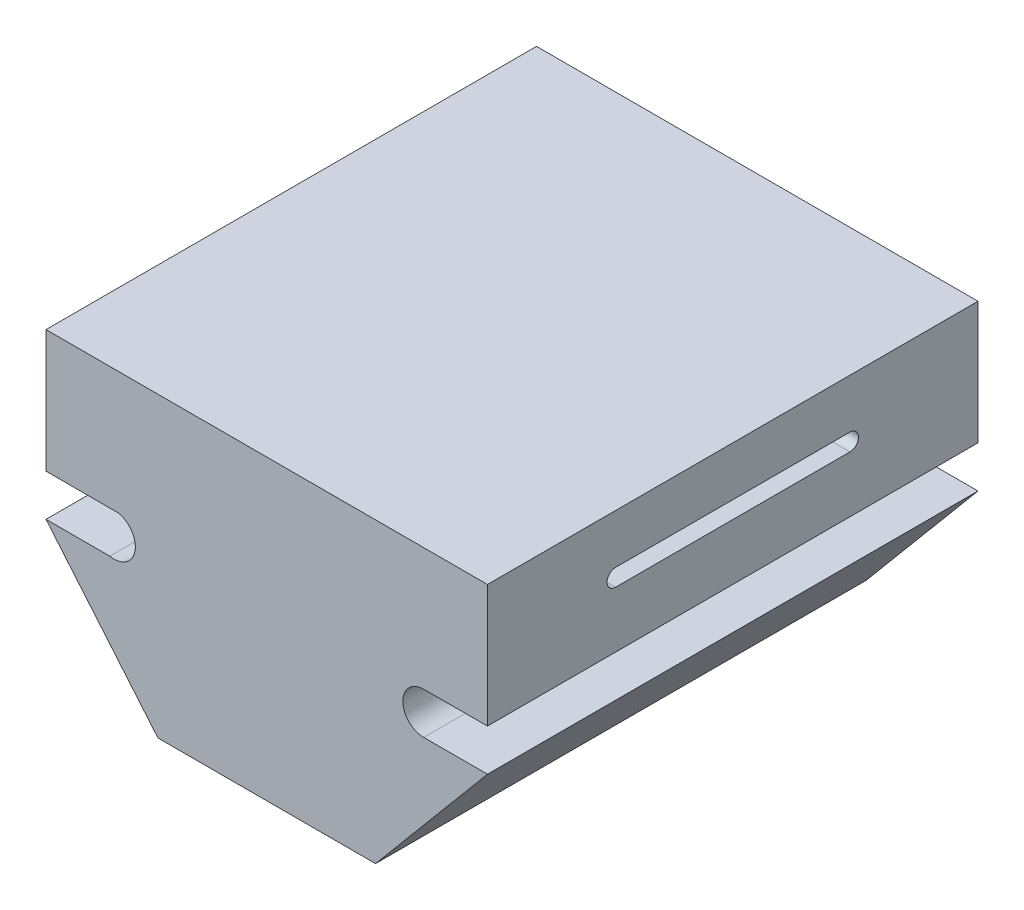
SolidWorks part; units mm, degrees
ref_plane "Front Plane" through (0, 0, 0) normal (0, 0, 1) x (1, 0, 0)
ref_plane "Top Plane" through (0, 0, 0) normal (0, 1, 0) x (1, 0, 0)
ref_plane "Right Plane" through (0, 0, 0) normal (1, 0, 0) x (0, 0, -1)
sketch "Sketch2" plane through (0, 0, 0) normal (0, 0, 1) x (1, 0, 0)
  line L0 (-7.6345, 10.269) -> (28.3655, 10.269)
  line L1 (28.3655, 10.269) -> (28.3655, 0.269)
  line L2 (-7.6345, 10.269) -> (-7.6345, 0.269)
  line L3 (-7.6345, 0.269) -> (-1.7345, 0.269)
  line L4 (28.3655, 0.269) -> (23.1655, 0.269)
  line L5 (-7.6345, -3.131) -> (-2.4345, -3.131)
  line L6 (28.3655, -3.131) -> (23.1655, -3.131)
  line L7 (-7.6345, -3.131) -> (1.4931, -14.0089)
  line L8 (28.3655, -3.131) -> (19.2379, -14.0089)
  line L9 (1.4931, -14.0089) -> (19.2379, -14.0089)
  line L10 (-2.4345, -3.131) -> (23.1655, -3.131)
  arc A0 (-1.7345, 0.269) -> (-2.4345, -3.131) centre (-2.0845, -1.431) cw
  arc A1 (23.1655, 0.269) -> (23.1655, -3.131) centre (23.1655, -1.431) ccw
  dimension "D1" = 10
extrude "Boss-Extrude3" add sketch "Sketch2" along normal blind 40 contours A1 L4 L1 L0 L2 L3 A0 L10 | L10 A0 L5 L7 L9 L8 L6 region at (10.4008, 4.0935, 0) region at (10.3662, -7.9544, 0)
sketch "Sketch4" plane through (-7.6345, 0, 0) normal (-1, 0, 0) x (0, 0, 1)
  line L0 (10.45, 5.5511) -> (29.55, 5.5511) construction
  line L1 (10.45, 6.2511) -> (29.55, 6.2511)
  line L2 (10.45, 4.8511) -> (29.55, 4.8511)
  arc A0 (10.45, 6.2511) -> (10.45, 4.8511) centre (10.45, 5.5511) ccw
  arc A1 (29.55, 4.8511) -> (29.55, 6.2511) centre (29.55, 5.5511) ccw
  point P2 (20, 5.5511)
extrude "Cut-Extrude1" cut sketch "Sketch4" against normal blind 72
